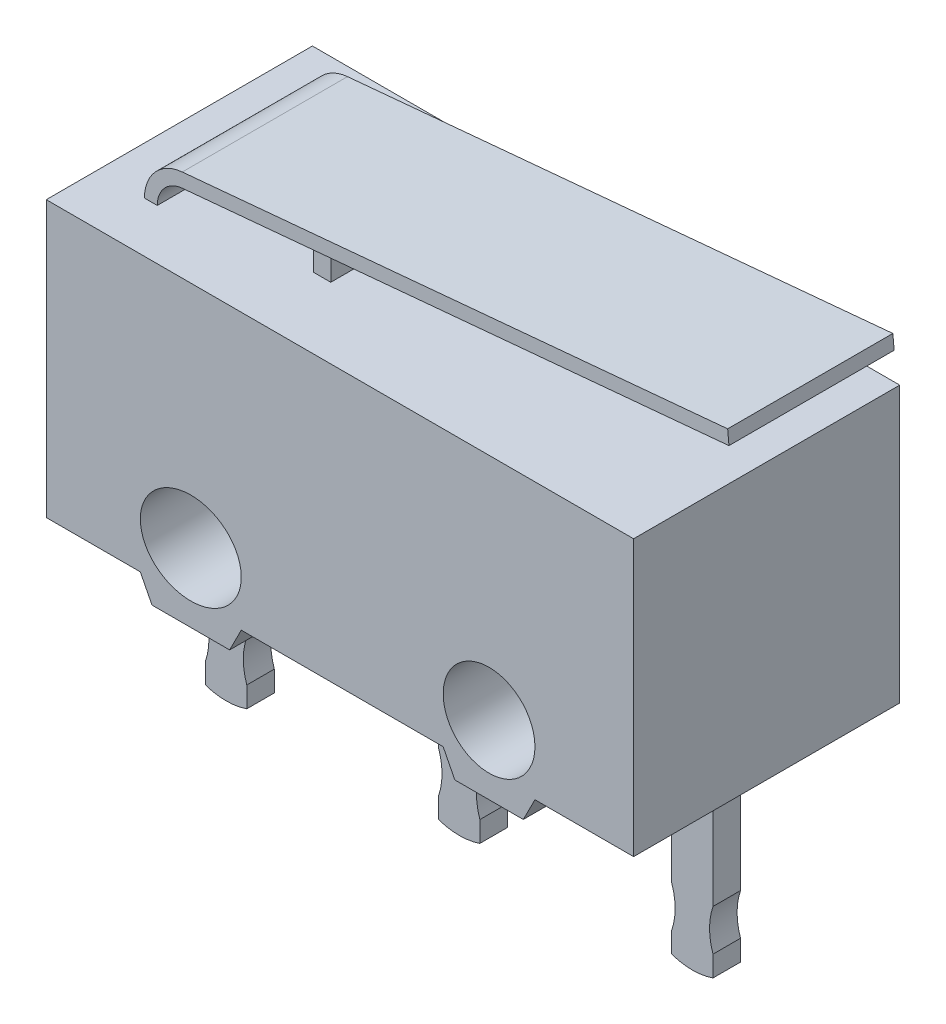
SolidWorks part; units mm, degrees
ref_plane "Front Plane" through (0, 0, 0) normal (0, 0, 1) x (1, 0, 0)
ref_plane "Top Plane" through (0, 0, 0) normal (0, 1, 0) x (1, 0, 0)
ref_plane "Right Plane" through (0, 0, 0) normal (1, 0, 0) x (0, 0, -1)
sketch "Sketch1" plane through (0, 0, 0) normal (0, 0, 1) x (1, 0, 0)
  line L0 (-3.25, -1.75) -> (3.25, -1.75) construction
  line L1 (-6.4, -3.25) -> (6.4, -3.25)
  line L2 (-6.4, -3.25) -> (-6.4, 3.25)
  line L3 (-6.4, 3.25) -> (6.4, 3.25)
  line L4 (6.4, -3.25) -> (6.4, 3.25)
  line L5 (-6.4, -3.25) -> (6.4, 3.25) construction
  line L6 (-6.4, 3.25) -> (6.4, -3.25) construction
  line L7 (-6.4, -2.75) -> (6.4, -2.75)
  line L8 (-4.223, -3) -> (-2.277, -3) construction
  line L9 (2.377, -3) -> (4.123, -3) construction
  line L10 (-2.4039, -3.25) -> (-2.15, -2.75)
  line L11 (-4.0961, -3.25) -> (-4.35, -2.75)
  line L12 (2.5039, -3.25) -> (2.25, -2.75)
  line L13 (3.9961, -3.25) -> (4.25, -2.75)
  line L14 (4.25, -1.75) -> (2.25, -1.75) construction
  line L15 (-5.08, -4.8) -> (0, -4.8) construction
  line L16 (-4.63, -6.85) -> (-5.53, -6.85)
  line L17 (-4.63, -6.85) -> (-4.63, -2.75)
  line L18 (-4.63, -2.75) -> (-5.53, -2.75)
  line L19 (-5.53, -6.85) -> (-5.53, -2.75)
  line L20 (-4.63, -6.85) -> (-5.53, -2.75) construction
  line L21 (-4.63, -2.75) -> (-5.53, -6.85) construction
  line L22 (-0.45, -6.85) -> (0.45, -6.85)
  line L23 (4.63, -6.85) -> (5.53, -6.85)
  line L24 (4.63, -6.85) -> (4.63, -2.75)
  line L25 (4.63, -2.75) -> (5.53, -2.75)
  line L26 (5.53, -6.85) -> (5.53, -2.75)
  line L27 (4.63, -6.85) -> (5.53, -2.75) construction
  line L28 (4.63, -2.75) -> (5.53, -6.85) construction
  line L29 (-0.45, -6.85) -> (-0.45, -2.75)
  line L30 (-0.45, -2.75) -> (0.45, -2.75)
  line L31 (0.45, -6.85) -> (0.45, -2.75)
  line L32 (-0.45, -6.85) -> (0.45, -2.75) construction
  line L33 (-0.45, -2.75) -> (0.45, -6.85) construction
  line L34 (0, -4.8) -> (5.08, -4.8) construction
  line L35 (-4.5356, 4.1542) -> (7.35, 5.25)
  line L36 (-1.9312, 3.25) -> (-1.9312, 4.0882) construction
  line L37 (7.35, 5.25) -> (7.378, 4.9465)
  line L38 (7.378, 4.9465) -> (-4.5356, 3.8481)
  line L39 (-1.7407, 3.885) -> (-1.7407, 3.25)
  line L40 (-2.1217, 3.885) -> (-2.1217, 3.25)
  circle A0 centre (3.25, -1.75) radius 1
  arc A1 (-4.5356, 4.1542) -> (-5.3602, 3.25) centre (-4.4522, 3.25) ccw
  arc A2 (-4.5356, 3.8481) -> (-5.081, 3.25) centre (-4.4804, 3.25) ccw
  arc A3 (-2.1217, 3.885) -> (-1.7407, 3.885) centre (-1.9312, 3.885) cw
  ellipse E0 centre (-3.25, -1.75) end of major axis (-2.15, -1.75) minor radius 1
  point P0 (0, 0)
  point P8 (0, -1.75)
  point P21 (0, -4.8)
  point P24 (-2.277, -3)
  point P27 (-4.223, -3)
  point P30 (2.377, -3)
  point P33 (4.123, -3)
  point P34 (5.08, -4.8)
  point P36 (-5.08, -4.8)
  point P38 (-3.25, -3)
  point P39 (3.25, -3)
  dimension "D3" = 2
  dimension "D6" = 1.5
  dimension "D8" = 3.6
  dimension "D12" = 7
  dimension "D18" = 0.1905
  dimension "D19" = 0.0127
  dimension "D1" = 6.5
  dimension "D2" = 12.8
  dimension "D4" = 2
  dimension "D5" = 2.2
  dimension "D7" = 6.5
  dimension "D9" = 0.9
  dimension "D10" = 5.08
  dimension "D11" = 0.5
  dimension "D13" = 10.6
  dimension "D14" = 11.7602
  dimension "D15" = 8.3312
  dimension "D16" = 0.8382
  dimension "D17" = 0.3048
extrude "Boss-Extrude1" add sketch "Sketch1" along normal mid plane 5.8 contours L7 E0 A0 L4 L3 L2 | L11 L1 L10 L7 | L1 L13 L7 L12 region at (-3.25, -2.9891, 0) region at (0.0145, 0.438, 0) region at (3.25, -2.9879, 0)
extrude "Boss-Extrude2" add sketch "Sketch1<3>" along normal mid plane 3.6 contours A2 L38 L37 L35 A1 L3 region at (0.8957, 4.4827, 0)
sketch "Sketch1<3>" plane through (0, 0, 0) normal (0, 0, 1) x (1, 0, 0) same geometry as "Sketch1"
extrude "Boss-Extrude3" add sketch "Sketch1<4>" along normal mid plane 2.7178 contours A3 L40 L3 L39 region at (-1.9312, 3.6435, 0)
sketch "Sketch1<4>" plane through (0, 0, 0) normal (0, 0, 1) x (1, 0, 0) same geometry as "Sketch1"
extrude "Boss-Extrude4" add sketch "Sketch1<5>" along normal mid plane 0.6 separate body contours L23 L26 L1 L24 | L22 L31 L1 L29 | L19 L16 L17 L1 | L29 L22 L31 L30 | L24 L23 L26 L25 | L17 L16 L19 L18 region at (-5.08, -5.05, 0) region at (0, -5.05, 0) region at (5.08, -5.05, 0)
sketch "Sketch1<5>" plane through (0, 0, 0) normal (0, 0, 1) x (1, 0, 0) same geometry as "Sketch1"
sketch "Sketch2" plane through (0, 0, 0) normal (0, 0, 1) x (1, 0, 0)
  line L0 (4.63, -6.85) -> (5.53, -6.85) construction
  line L1 (5.53, -6.85) -> (5.53, -2.75) construction
  line L2 (4.63, -6.85) -> (4.63, -2.75) construction
  line L3 (4.63, -2.75) -> (5.53, -2.75) construction
  line L4 (0.45, -6.85) -> (0.45, -2.75) construction
  line L5 (-0.45, -6.85) -> (0.45, -6.85) construction
  line L6 (-0.45, -6.85) -> (-0.45, -2.75) construction
  line L7 (-0.45, -2.75) -> (0.45, -2.75) construction
  line L8 (-4.63, -6.85) -> (-5.53, -6.85) construction
  line L9 (-5.53, -6.85) -> (-5.53, -2.75) construction
  line L10 (-4.63, -6.85) -> (-4.63, -2.75) construction
  line L11 (-4.63, -2.75) -> (-5.53, -2.75) construction
  line L12 (4.63, -6.85) -> (5.53, -6.85)
  line L13 (5.53, -6.85) -> (5.53, -2.75)
  line L14 (4.63, -6.85) -> (4.63, -2.75)
  line L15 (4.63, -2.75) -> (5.53, -2.75)
  line L16 (0.45, -6.85) -> (0.45, -2.75)
  line L17 (-0.45, -6.85) -> (0.45, -6.85)
  line L18 (-0.45, -6.85) -> (-0.45, -2.75)
  line L19 (-0.45, -2.75) -> (0.45, -2.75)
  line L20 (-4.63, -6.85) -> (-5.53, -6.85)
  line L21 (-5.53, -6.85) -> (-5.53, -2.75)
  line L22 (-4.63, -6.85) -> (-4.63, -2.75)
  line L23 (-4.63, -2.75) -> (-5.53, -2.75)
  line L24 (-4.44, -2.75) -> (-4.44, -3)
  line L25 (-6.4, -2.75) -> (-4.35, -2.75) construction
  line L26 (-4.44, -3) -> (-4.63, -3.19)
  line L27 (0.64, -2.75) -> (0.64, -3)
  line L28 (-2.15, -2.75) -> (2.25, -2.75) construction
  line L29 (0.64, -3) -> (0.45, -3.19)
  line L30 (4.44, -2.75) -> (4.44, -3)
  line L31 (4.25, -2.75) -> (6.4, -2.75) construction
  line L32 (4.44, -3) -> (4.63, -3.19)
  line L33 (3.9961, -3.25) -> (4.25, -2.75) construction
  line L34 (4.25, -2.75) -> (4.44, -2.875) construction
  line L35 (4.44, -2.875) -> (4.63, -2.75) construction
  line L36 (4.535, -3.095) -> (4.535, -2.905) construction
  line L37 (4.44, -3) -> (4.63, -2.81) construction
  line L38 (4.535, -2.905) -> (4.63, -3) construction
  line L39 (4.63, -3) -> (4.535, -3.095) construction
  line L40 (-0.375, -5.875) -> (-0.45, -5.875) construction
  line L41 (-0.45, -5.875) -> (-4.63, -5.875) construction
  line L42 (-4.63, -5.875) -> (-4.63, -6.85) construction
  line L43 (-4.63, -6.85) -> (-0.45, -6.85) construction
  line L44 (-2.54, -6.85) -> (-2.54, -6.775) construction
  line L45 (-2.54, -6.775) -> (-4.63, -6.775) construction
  line L46 (-4.63, -2.75) -> (-4.44, -2.75)
  line L47 (0.45, -2.75) -> (0.64, -2.75)
  line L48 (4.44, -2.75) -> (4.63, -2.75)
  arc A0 (-0.45, -6.775) -> (0.45, -6.775) centre (0, -5.4625) ccw
  arc A1 (-5.53, -6.775) -> (-4.63, -6.775) centre (-5.08, -5.4625) ccw
  arc A2 (4.63, -6.775) -> (5.53, -6.775) centre (5.08, -5.4625) ccw
  arc A5 (-0.45, -5.425) -> (-0.45, -6.325) centre (-1.7625, -5.875) cw
  arc A6 (0.45, -5.425) -> (0.45, -6.325) centre (1.7625, -5.875) ccw
  arc A7 (4.63, -5.425) -> (4.63, -6.325) centre (3.3175, -5.875) cw
  arc A8 (5.53, -5.425) -> (5.53, -6.325) centre (6.8425, -5.875) ccw
  arc A9 (-5.53, -6.775) -> (-4.63, -6.775) centre (-5.08, -5.4625) ccw
  arc A10 (-4.63, -5.425) -> (-4.63, -6.325) centre (-3.3175, -5.875) ccw
  arc A11 (-5.53, -5.425) -> (-5.53, -6.325) centre (-6.8425, -5.875) cw
  point P30 (4.123, -3)
  point P36 (4.535, -2.905)
  dimension "D1" = 0.075
  dimension "D2" = 0.9
  dimension "D3" = 0.45
extrude "Cut-Extrude4" cut sketch "Sketch2" against normal through all both and the other way through all contours L13 A8 | A7 L14 | A2 L12 L13 | A2 L14 L12 | L16 A6 | A5 L18 | A0 L18 L17 | A0 L17 L16 | L22 A10 | A1 L20 L22 | A1 L21 L20 | A11 L21 region at (4.7419, -6.8276, 0) region at (5.4181, -6.8276, 0) region at (4.6601, -5.875, 0) region at (5.4999, -5.875, 0) region at (0.3381, -6.8276, 0) region at (-0.3381, -6.8276, 0) region at (0.4199, -5.875, 0) region at (-0.4199, -5.875, 0) region at (-4.7419, -6.8276, 0) region at (-5.4181, -6.8276, 0) region at (-4.6601, -5.875, 0) region at (-5.4999, -5.875, 0)
extrude "Cut-Extrude5" cut sketch "Sketch2<4>" against normal through all both and the other way through all contours L22 A10 | A1 L20 L22 | A1 L21 L20 | A11 L21 region at (-4.7419, -6.8276, 0) region at (-5.4181, -6.8276, 0) region at (-4.6601, -5.875, 0) region at (-5.4999, -5.875, 0)
sketch "Sketch2<4>" plane through (0, 0, 0) normal (0, 0, 1) x (1, 0, 0) same geometry as "Sketch2"
extrude "Cut-Extrude6" cut sketch "Sketch2<5>" against normal through all both and the other way through all contours A7 L14 | L13 A8 | A2 L12 L13 | A2 L14 L12 region at (4.7419, -6.8276, 0) region at (5.4181, -6.8276, 0) region at (4.6601, -5.875, 0) region at (5.4999, -5.875, 0)
sketch "Sketch2<5>" plane through (0, 0, 0) normal (0, 0, 1) x (1, 0, 0) same geometry as "Sketch2"
extrude "Boss-Extrude5" add sketch "Sketch2<7>" along normal up to surface (0.3 mm away) and the other way up to surface (0.3 mm away) contours L48 L30 L32 L14 | L47 L16 L29 L27 | L46 L22 L26 L24 region at (4.5437, -2.9269, 0) region at (0.5363, -2.9269, 0) region at (-4.5437, -2.9269, 0) up to face at (5.08, -5.3281, 0.3) other way up to face at (-5.08, -5.3281, -0.3)
sketch "Sketch2<7>" plane through (0, 0, 0) normal (0, 0, 1) x (1, 0, 0) same geometry as "Sketch2"
